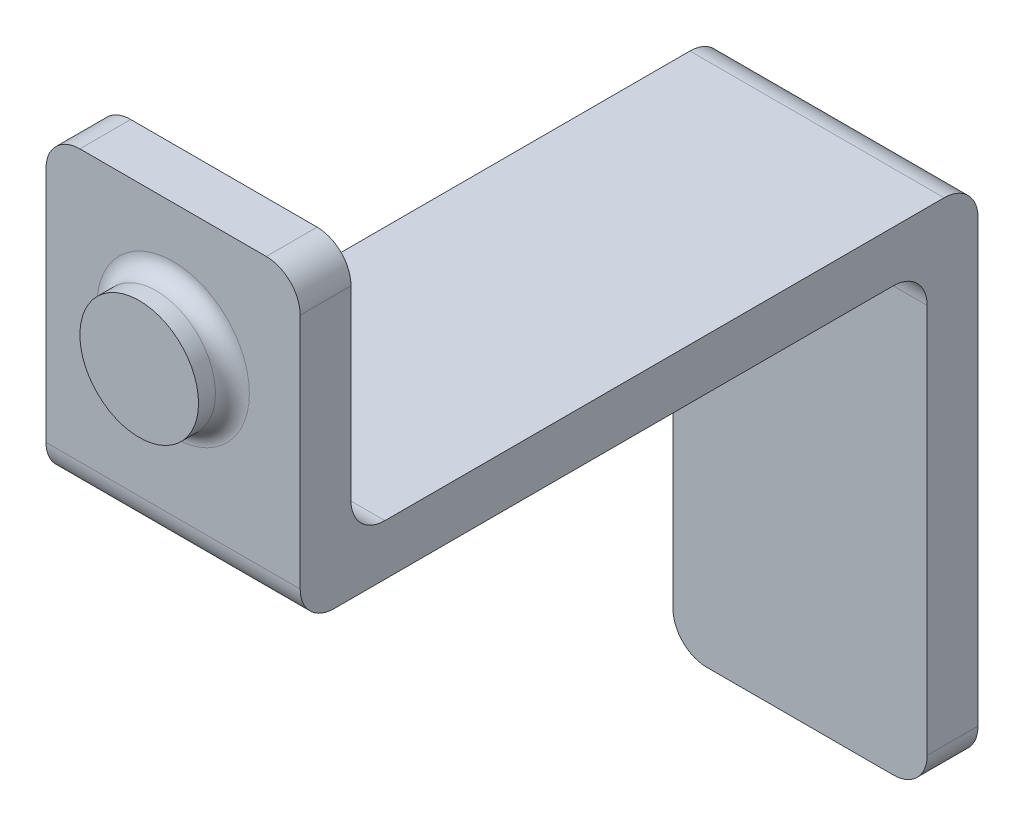
SolidWorks part; units mm, degrees
material "ABS"
ref_plane "前基準面" through (0, 0, 0) normal (0, 0, 1) x (1, 0, 0)
ref_plane "上基準面" through (0, 0, 0) normal (0, 1, 0) x (1, 0, 0)
ref_plane "右基準面" through (0, 0, 0) normal (1, 0, 0) x (0, 0, -1)
sketch "草圖1" plane through (0, 0, 0) normal (1, 0, 0) x (0, 0, -1)
  line L0 (-34, 18) -> (-34, 3)
  line L1 (-34, 3) -> (3, 3)
  line L2 (55, 0) -> (-55, 0) construction
  line L3 (0, 55) -> (0, -55) construction
  line L4 (3, 3) -> (3, -27)
  line L5 (3, -27) -> (0, -27)
  line L6 (0, -27) -> (0, 0)
  line L7 (0, 0) -> (-37, 0)
  line L8 (-37, 0) -> (-37, 18)
  line L9 (-37, 18) -> (-34, 18)
  dimension "D1" = 3
  dimension "D2" = 3
  dimension "D3" = 30
  dimension "D4" = 37
  dimension "D5" = 15
extrude "填料-伸長1" add sketch "草圖1" along normal blind 7.5 and the other way blind 7.5
fillet "圓角1" radius 2 8 edges at (-7.5, -27, -1.5) (7.5, -27, -1.5) (-7.5, 18, 35.5) (7.5, 18, 35.5) (0, 3, -3) (0, 3, 34) (0, 0, 37) (0, 0, 0)
sketch "草圖2" plane through (0, 0, 37) normal (0, 0, 1) x (1, 0, 0)
  line L1 (-7.5, 3) -> (7.5, 3) construction
  line L2 (-7.5, 3) -> (7.5, 3)
  line L5 (5.5, 18) -> (-5.5, 18)
  line L6 (-7.5, 16) -> (-7.5, 2)
  line L7 (-7.5, 2) -> (7.5, 2)
  line L8 (7.5, 2) -> (7.5, 16)
  line L9 (5.5, 18) -> (-5.5, 18)
  line L10 (-7.5, 16) -> (-7.5, 2)
  line L11 (-7.5, 2) -> (7.5, 2)
  line L12 (7.5, 2) -> (7.5, 16)
  circle A0 centre (0, 10.5) radius 3.5
  circle A1 centre (0, 10.5) radius 2.025 construction
  arc A4 (-5.5, 18) -> (-7.5, 16) centre (-5.5, 16) ccw
  arc A5 (7.5, 16) -> (5.5, 18) centre (5.5, 16) ccw
  arc A6 (-5.5, 18) -> (-7.5, 16) centre (-5.5, 16) ccw
  arc A7 (7.5, 16) -> (5.5, 18) centre (5.5, 16) ccw
  dimension "D1" = 7
  dimension "D2" = 4.05
  dimension "D4" = 7.5
  dimension "D3" = 0
  dimension "D5" = 15
extrude "填料-伸長3" add sketch "草圖2" along normal blind 2 contours A0 region at (0, 10.5, 37)
sketch "草圖4" plane through (0, 0, 34) normal (0, 0, -1) x (-1, 0, 0)
  circle A0 centre (0, 10.5) radius 3.5 construction
  circle A1 centre (0, 10.5) radius 3.5 construction
  circle A2 centre (0, 10.5) radius 2.025
  dimension "D1" = 4.05
extrude "除料-伸長1" cut sketch "草圖4" against normal blind 4
fillet "圓角2" radius 1 1 edges at (3.5, 10.5, 37)
